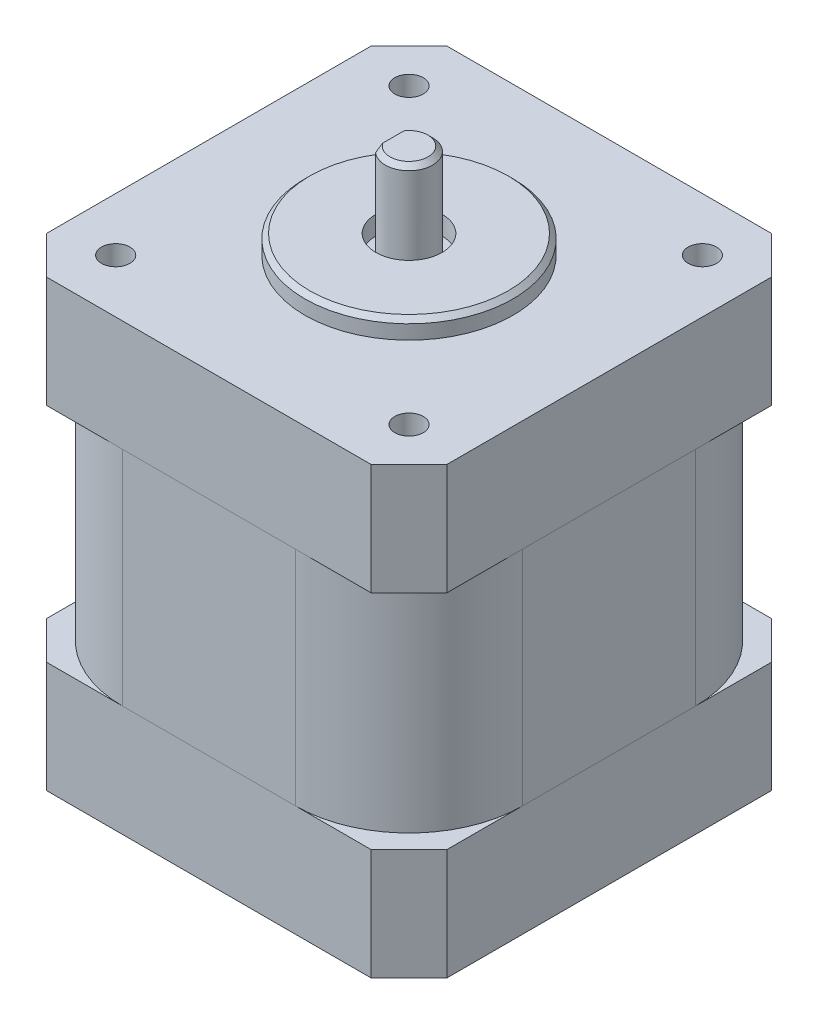
SolidWorks part; units mm, degrees
ref_plane "Front (XY)" through (0, 0, 0) normal (0, 0, 1) x (1, 0, 0)
ref_plane "Top (XZ)" through (0, 0, 0) normal (0, 1, 0) x (1, 0, 0)
ref_plane "Right (YZ)" through (0, 0, 0) normal (1, 0, 0) x (0, 0, -1)
sketch "Sketch1" plane through (0, 0, 0) normal (0, 1, 0) x (1, 0, 0)
  line L0 (-21.15, 21.15) -> (-21.15, -21.15)
  line L1 (-21.15, -21.15) -> (21.15, -21.15)
  line L2 (21.15, -21.15) -> (21.15, 21.15)
  line L3 (21.15, 21.15) -> (-21.15, 21.15)
  point P3 (0, 21.15)
  point P6 (21.15, 0)
  dimension "D1" = 42.3
  dimension "D2" = 42.3
extrude "Boss-Extrude1" add sketch "Sketch1" along normal blind 11.75
ref_plane "Plane1" through (0, 11.75, 0) normal (0, 1, 0) x (1, 0, 0)
sketch "Sketch2" plane through (0, 11.75, 0) normal (0, 1, 0) x (1, 0, 0)
  line L0 (-21.15, 21.15) -> (-21.15, -21.15)
  line L1 (-21.15, -21.15) -> (21.15, -21.15)
  line L2 (21.15, -21.15) -> (21.15, 21.15)
  line L3 (21.15, 21.15) -> (-21.15, 21.15)
  point P3 (0, 21.15)
  point P5 (21.15, 0)
  dimension "D1" = 42.3
  dimension "D2" = 42.3
extrude "Boss-Extrude2" add sketch "Sketch2" along normal blind 23.5 separate body
fillet "Fillet2" radius 12 4 edges at (21.15, 23.5, 21.15) (21.15, 23.5, -21.15) (-21.15, 23.5, -21.15) (-21.15, 23.5, 21.15)
sketch "Sketch4" plane through (0, 0, 0) normal (0, 1, 0) x (1, 0, 0)
  line L0 (-21.15, 21.15) -> (-21.15, -21.15)
  line L1 (-21.15, -21.15) -> (21.15, -21.15)
  line L2 (21.15, -21.15) -> (21.15, 21.15)
  line L3 (21.15, 21.15) -> (-21.15, 21.15)
extrude "Boss-Extrude3" add sketch "Sketch4" along normal blind 11.75
ref_plane "Plane2" through (0, 35.25, 0) normal (0, 1, 0) x (1, 0, 0)
sketch "Sketch6" plane through (0, 35.25, 0) normal (0, 1, 0) x (1, 0, 0)
  line L0 (-21.15, 21.15) -> (-21.15, -21.15)
  line L1 (-21.15, -21.15) -> (21.15, -21.15)
  line L2 (21.15, -21.15) -> (21.15, 21.15)
  line L3 (21.15, 21.15) -> (-21.15, 21.15)
  point P3 (0, 21.15)
  point P5 (21.15, 0)
  dimension "D1" = 42.3
  dimension "D2" = 42.3
extrude "Boss-Extrude4" add sketch "Sketch6" along normal blind 11.75
chamfer "Chamfer3" distance 4 angle 45 4 edges at (-21.15, 5.875, -21.15) (21.15, 5.875, -21.15) (-21.15, 5.875, 21.15) (21.15, 5.875, 21.15)
chamfer "Chamfer4" distance 4 angle 45 4 edges at (-21.15, 41.125, 21.15) (21.15, 41.125, 21.15) (-21.15, 41.125, -21.15) (21.15, 41.125, -21.15)
ref_plane "Plane3" through (0, 47, 0) normal (0, 1, 0) x (1, 0, 0)
sketch "Sketch7" plane through (0, 47, 0) normal (0, 1, 0) x (1, 0, 0)
  circle A0 centre (0, 0) radius 11
  dimension "D1" = 22
extrude "Boss-Extrude5" add sketch "Sketch7" along normal blind 2
sketch "Sketch8" plane through (0, 47, 0) normal (0, 1, 0) x (1, 0, 0)
  circle A0 centre (0, 0) radius 2.5
  dimension "D1" = 5
extrude "Boss-Extrude6" add sketch "Sketch8" along normal blind 10
chamfer "Chamfer5" distance 0.5 angle 45 1 edges at (0, 57, 2.5)
chamfer "Chamfer9" distance 0.5 angle 45 1 edges at (0, 49, 11)
sketch "Sketch15" plane through (0, 0, 0) normal (0, 0, 1) x (1, 0, 0)
  line L0 (0, 0) -> (0, 47) construction
  line L2 (2.5, 49.5) -> (3.5002, 49.5)
  line L3 (3.5002, 49.5) -> (3.5002, 47)
  line L4 (3.5002, 47) -> (2.5, 47)
  line L5 (2.5, 47) -> (2.5, 49.5)
  dimension "D1" = 1.0002
  dimension "D2" = 2.5
  dimension "D3" = 2.5
  dimension "D4" = 47
revolve "Cut-Revolve1" cut sketch "Sketch15" angle 360 about L0
sketch "Sketch10" plane through (0, 0, 0) normal (0, 0, 1) x (1, 0, 0)
  line L0 (-2.5, 56.5) -> (-2.5, 47) construction
  line L1 (-2.5, 56.5) -> (-2.5, 55.5)
  line L2 (2, 57) -> (-2, 57) construction
  line L3 (-2, 57) -> (-2.5, 56.5) construction
  line L4 (-1.65, 57) -> (-2, 57)
  line L5 (-2, 57) -> (-2.5, 56.5)
  line L6 (-2.5, 55.5) -> (-1.65, 55.5)
  line L7 (-1.65, 55.5) -> (-1.65, 57)
  dimension "D1" = 0.85
  dimension "D2" = 55.5
extrude "Cut-Extrude1" [suppressed] cut sketch "Sketch10" against normal through all both and the other way through all
chamfer "Chamfer10" [suppressed] distance 1 angle 45
sketch "Sketch17" [suppressed] plane through (0, 47, 0) normal (0, 1, 0) x (1, 0, 0)
  circle A0 centre (15.5, 15.5) radius 1.5
  circle A1 centre (15.5, -15.5) radius 1.5
  circle A2 centre (-15.5, -15.5) radius 1.5
  circle A3 centre (-15.5, 15.5) radius 1.5
  dimension "D1" = 3
  dimension "D2" = 31
  dimension "D3" = 31
  dimension "D4" = 15.5
  dimension "D5" = 15.5
extrude "Cut-Extrude3" [suppressed] cut sketch "Sketch17" against normal blind 10
sketch "Sketch18" plane through (0, 47, 0) normal (0, 1, 0) x (1, 0, 0)
  circle A0 centre (15.5, 15.5039) radius 1.5
  circle A1 centre (15.5, -15.4961) radius 1.5
  circle A2 centre (-15.5, -15.4961) radius 1.5
  circle A3 centre (-15.5, 15.5039) radius 1.5
  dimension "D1" = 3
  dimension "D2" = 31
  dimension "D3" = 31
  dimension "D4" = 15.4961
  dimension "D5" = 15.5
extrude "Cut-Extrude4" cut sketch "Sketch18" against normal blind 10
sketch "Sketch19" plane through (0, 0, 0) normal (0, 0, 1) x (1, 0, 0)
  line L0 (-2.5, 56.5) -> (-2.5, 47) construction
  line L1 (-2, 57) -> (-2.5, 56.5) construction
  line L2 (2, 57) -> (-2, 57) construction
  line L3 (-2.5, 56.5) -> (-2.5, 49)
  line L4 (-2, 57) -> (-2.5, 56.5)
  line L5 (-1.65, 57) -> (-2, 57)
  line L6 (-2.5, 49) -> (-1.65, 49)
  line L7 (-1.65, 49) -> (-1.65, 57)
  dimension "D1" = 8
  dimension "D2" = 0.85
extrude "Cut-Extrude5" cut sketch "Sketch19" against normal through all both and the other way through all
chamfer "Chamfer11" distance 1 angle 45 1 edges at (-1.65, 49, 0)
